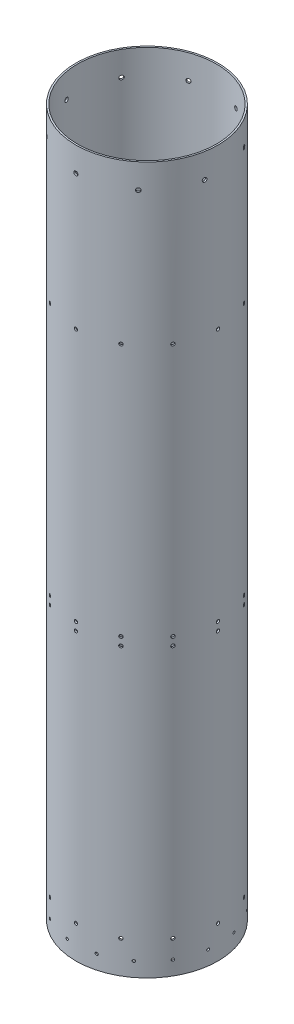
SolidWorks part; units mm, degrees
material "E-Glass Fiber"
ref_plane "Płaszczyzna przednia" through (0, 0, 0) normal (0, 0, 1) x (1, 0, 0)
ref_plane "Płaszczyzna górna" through (0, 0, 0) normal (0, 1, 0) x (1, 0, 0)
ref_plane "Płaszczyzna prawa" through (0, 0, 0) normal (1, 0, 0) x (0, 0, -1)
sketch "Szkic1" plane through (0, 0, 0) normal (0, 1, 0) x (1, 0, 0)
  circle A0 centre (0, 0) radius 85
  circle A1 centre (0, 0) radius 87
  dimension "D1" = 170
  dimension "D2" = 174
extrude "Dodanie-wyciągnięcie2" add sketch "Szkic1" along normal blind 865
sketch3d "Szkic 3D1" plane through (0, 0, 0) normal (0, 0, 1) x (1, 0, 0)
sketch "Szkic3" plane through (0, 0, 87) normal (0, 0, 1) x (1, 0, 0)
  line L0 (0, 0) -> (0, 49.8768) construction
  line L1 (-87, 0) -> (87, 0) construction
  circle A1 centre (0, 40) radius 2
  dimension "D3" = 4
  dimension "D2" = 40
extrude "Wytnij-wyciągnięcie1" cut sketch "Szkic3" against normal up to next
pattern_circular "Szyk kołowy1" count 12 over 360 about axis through (0, 865, 0) along (0, -1, 0) of "Wytnij-wyciągnięcie1" reverse direction yes
pattern_linear "Szyk liniowy1" count 2 spacing 310 along (0, 1, 0) of "Szyk kołowy1"
pattern_linear "Szyk liniowy2" count 2 spacing 320 along (0, 1, 0) of "Szyk kołowy1"
pattern_linear "Szyk liniowy4" count 2 spacing 630 along (0, 1, 0) of "Szyk kołowy1"
sketch "Szkic8" plane through (0, 0, 87) normal (0, 0, 1) x (1, 0, 0)
  line L0 (0, 884.2508) -> (0, 790.1423) construction
  circle A0 centre (0, 835) radius 2.5
  circle A1 centre (0, 670) radius 2 construction
  dimension "D1" = 5
  dimension "D2" = 165
extrude "Wytnij-wyciągnięcie6" cut sketch "Szkic8" against normal blind 10
pattern_circular "Szyk kołowy5" count 9 over 360 about axis through (0, 865, 0) along (0, -1, 0) of "Wytnij-wyciągnięcie6"
sketch "Szkic9" plane through (0, 0, 0) normal (0, -1, 0) x (1, 0, 0)
  line L0 (0, 87) -> (0, 0) construction
  line L1 (0, 0) -> (22.5173, 84.0355) construction
  circle A0 centre (0, 0) radius 87 construction
  circle A1 centre (0, 0) radius 87
  dimension "D1" = 15
sketch3d "Szkic 3D2"
sketch "Szkic11" plane through (22.5173, 0, 84.0355) normal (0.2588, 0, 0.9659) x (0.9659, 0, -0.2588)
  line L0 (0, -8.8009) -> (0, 55.5169) construction
  line L1 (-87, 0) -> (87, 0) construction
  circle A0 centre (0, 17.5) radius 1.6
  dimension "D1" = 3.2
  dimension "D2" = 17.5
extrude "Wytnij-wyciągnięcie7" cut sketch "Szkic11" against normal blind 10
pattern_circular "Szyk kołowy6" count 16 over 360 about axis through (0, 865, 0) along (0, -1, 0) of "Wytnij-wyciągnięcie7" reverse direction yes
